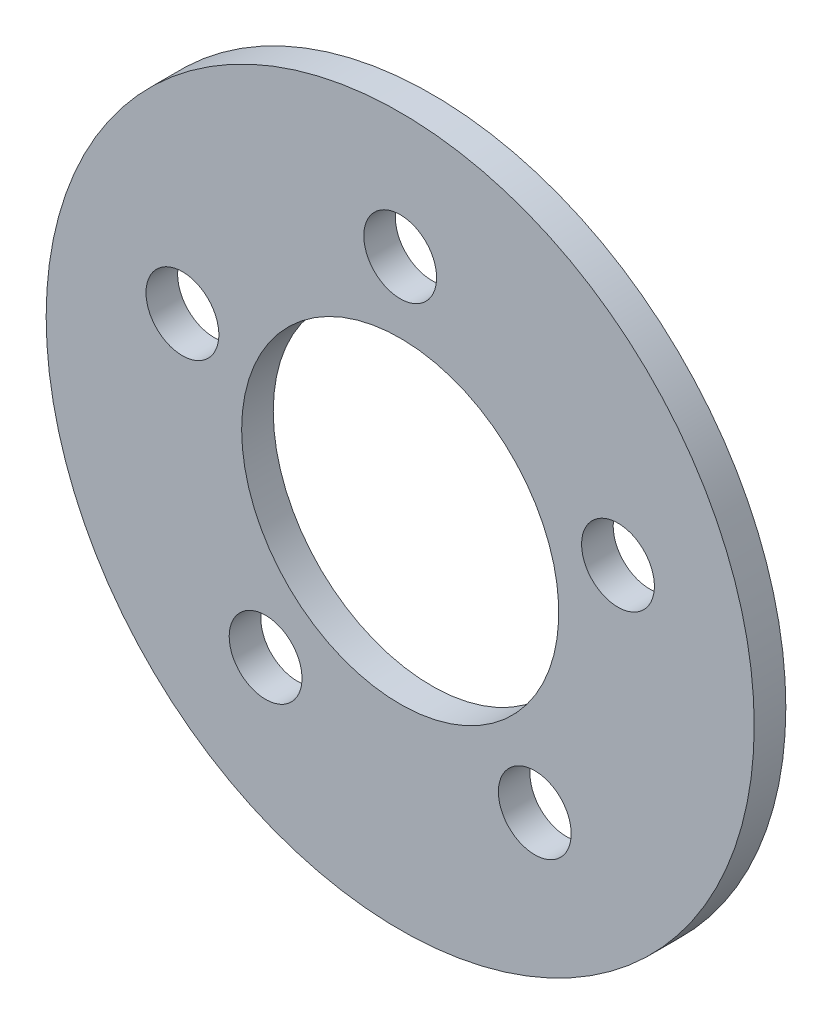
SolidWorks part; units mm, degrees
ref_plane "Front Plane" through (0, 0, 0) normal (0, 0, 1) x (1, 0, 0)
ref_plane "Top Plane" through (0, 0, 0) normal (0, 1, 0) x (1, 0, 0)
ref_plane "Right Plane" through (0, 0, 0) normal (1, 0, 0) x (0, 0, -1)
sketch "Sketch3" plane through (0, 0, -12.7) normal (0, 0, -1) x (-1, 0, 0)
  circle A0 centre (0, 0) radius 7.9629 construction
  circle A1 centre (0, 0) radius 7.9629
  circle A2 centre (0, 0) radius 17.78
  circle A3 centre (-6.7595, -9.3037) radius 1.8288 construction
  circle A4 centre (6.7595, -9.3037) radius 1.8288 construction
  circle A5 centre (10.9371, 3.5537) radius 1.8288 construction
  circle A6 centre (0, 11.5) radius 1.8288 construction
  circle A7 centre (-10.9371, 3.5537) radius 1.8288 construction
  circle A8 centre (-6.7595, -9.3037) radius 1.8288
  circle A9 centre (6.7595, -9.3037) radius 1.8288
  circle A10 centre (10.9371, 3.5537) radius 1.8288
  circle A11 centre (0, 11.5) radius 1.8288
  circle A12 centre (-10.9371, 3.5537) radius 1.8288
  dimension "D1" = 35.56
extrude "Boss-Extrude2" add sketch "Sketch3" along normal blind 1.5875
